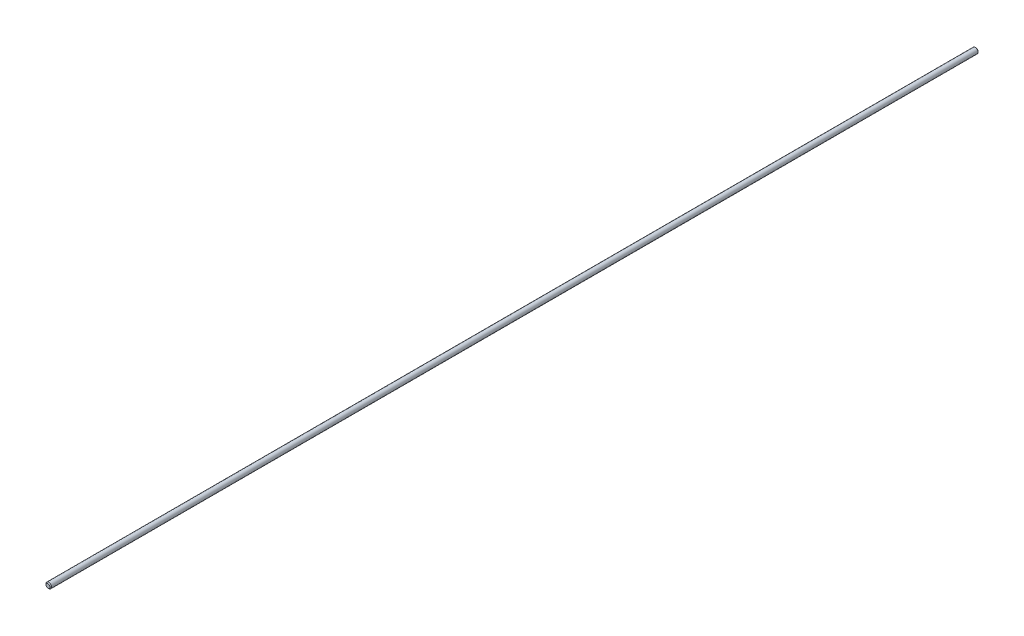
SolidWorks part; units mm, degrees
material "AISI 316 Stainless Steel Sheet (SS)"
ref_plane "Front Plane" through (0, 0, 0) normal (0, 0, 1) x (1, 0, 0)
ref_plane "Top Plane" through (0, 0, 0) normal (0, 1, 0) x (1, 0, 0)
ref_plane "Right Plane" through (0, 0, 0) normal (1, 0, 0) x (0, 0, -1)
sketch "Sketch1" plane through (0, 0, 0) normal (1, 0, 0) x (0, 0, -1)
  line L0 (-266.065, 0) -> (266.065, 0) construction
  line L1 (-266.065, 0) -> (-266.065, 1.5875)
  line L2 (-266.065, 1.5875) -> (266.065, 1.5875)
  line L3 (266.065, 1.5875) -> (266.065, 0)
  line L4 (266.6603, 1.1063) -> (266.3428, 1.6562) construction
  line L5 (266.3428, 1.6562) -> (266.0253, 1.1063) construction
  line L6 (266.0253, 1.1063) -> (266.6603, 1.1063) construction
  line L7 (266.6206, 1.1751) -> (266.065, 1.1751) construction
  line L8 (266.3428, 1.1063) -> (266.3428, 1.1751) construction
  line L9 (266.3428, 1.1751) -> (266.3428, 1.5875) construction
  line L10 (266.3428, 1.5875) -> (266.3428, 1.6562) construction
  line L15 (266.3825, 1.5875) -> (266.3031, 1.5875)
  line L16 (266.6405, 1.1407) -> (266.0452, 1.1407)
  line L17 (266.3031, 1.5875) -> (266.0452, 1.1407)
  line L18 (266.3825, 1.5875) -> (266.6405, 1.1407)
  line L19 (266.065, 0) -> (266.065, -1.5875) construction
  point P17 (266.3428, 1.1407)
  point P18 (253.365, 0)
  point P19 (264.795, -1.5875)
  point P20 (240.665, 0)
  point P22 (-253.365, 0)
  dimension "Length" = 532.13
  dimension "Thread size" = 3.175
  dimension "Pitch" = 0.635
  dimension "D2" = 0.0794
  dimension "D1" = 1.27
  dimension "Segment" = 25.4
  dimension "D3" = 12.7
  dimension "D4" = 12.7
sketch "Sketch2" plane through (0, 0, 0) normal (1, 0, 0) x (0, 0, -1)
  line L0 (266.065, 1.5875) -> (266.065, 0) construction
  line L1 (-266.065, 1.5875) -> (266.065, 1.5875) construction
  line L2 (-266.065, 0) -> (-266.065, 1.5875) construction
  line L3 (266.065, 1.5875) -> (266.065, 0)
  line L4 (-266.065, 1.5875) -> (266.065, 1.5875)
  line L5 (-266.065, 0) -> (-266.065, 1.5875)
  line L6 (-266.065, 0) -> (266.065, 0)
revolve "Revolve1" add sketch "Sketch2" angle 360 about L6
chamfer "Chamfer1" distance 0.4763 angle 45 2 edges at (1.5875, 0, -266.065) (1.5875, 0, 266.065)
sketch "Sketch3" [suppressed] plane through (0, 0, -304.8) normal (0, 0, -1) x (-1, 0, 0)
  circle A0 centre (0, 0) radius 1.1751
extrude "Cut-Extrude1" [suppressed] cut sketch "Sketch3" against normal through all flip side to cut
sketch "Sketch4" [suppressed] plane through (0, 0, -304.8) normal (0, 0, -1) x (-1, 0, 0)
  circle A1 centre (0, 0) radius 1.1751
  circle A2 centre (0, 0) radius 1.1751
  dimension "D1" = 0
ref_plane "Plane1" [suppressed] through (0, 0, 304.8) normal (0, 0, 1) x (1, 0, 0)
curve "Helix/Spiral1" [suppressed] pitch 0.635 height 26.035 turns 41
sketch "Sketch5" [suppressed] plane through (0, 0, 0) normal (1, 0, 0) x (0, 0, -1)
  line L0 (305.1175, 1.5875) -> (305.0381, 1.5875) construction
  line L1 (305.0381, 1.5875) -> (304.7802, 1.1407) construction
  line L2 (305.3755, 1.1407) -> (304.7802, 1.1407) construction
  line L3 (305.1175, 1.5875) -> (305.3755, 1.1407) construction
  line L4 (305.1175, 1.5875) -> (305.0381, 1.5875)
  line L5 (305.0381, 1.5875) -> (304.7802, 1.1407)
  line L6 (305.3755, 1.1407) -> (304.7802, 1.1407)
  line L7 (305.1175, 1.5875) -> (305.3755, 1.1407)
sweep "Sweep1" [suppressed] add profiles "Sketch5" path "Helix/Spiral1"
pattern_linear "LPattern1" [suppressed] count 22 spacing 25.4 along (0, 0, 1) of bodies 136
other "SurfaceCut1" [suppressed]
sketch "Sketch6" [suppressed] plane through (0, 0, 0) normal (1, 0, 0) x (0, 0, -1)
  line L0 (304.8, 1.1112) -> (304.3237, 1.5875)
  line L1 (304.8, 1.5875) -> (304.8, 0) construction
  line L3 (-304.8, 1.5875) -> (304.8, 1.5875) construction
  line L4 (304.3237, 1.5875) -> (304.3238, 1.6562)
  line L5 (304.3238, 1.6562) -> (305.3953, 1.6562)
  line L6 (305.3953, 1.6562) -> (305.3953, 1.1112)
  line L7 (305.3953, 1.1112) -> (304.8, 1.1112)
  dimension "D1" = 45
  dimension "D2" = 0.4763
revolve "Cut-Revolve1" [suppressed] cut sketch "Sketch6" angle 360 about L0
mirror "Mirror1" [suppressed] about plane through (0, 0, 0) normal (0, 0, 1)
sketch "Sketch7" plane through (0, 0, -266.065) normal (0, 0, -1) x (-1, 0, 0)
  circle A0 centre (0, 0) radius 6.5324
extrude "Cut-Extrude2" [suppressed] cut sketch "Sketch7" against normal blind 35.306
ref_axis "Axis1" through (0, 0, 312.5597) along (0, 0, -1)
equation "\"D2@Sketch1\"=\"Pitch@Sketch1\"/8"
equation "\"D2@Sketch1\" = \"Pitch@Sketch1\" / 8"
equation "\"D1@Sketch1\"=\"Pitch@Sketch1\"*2"
equation "\"Segment@Sketch1\" = \"Pitch@Sketch1\" * 40"
equation "\"D4@Sketch1\"=\"D3@Sketch1\""
equation "\"D1@Chamfer1\"=\"pitch@sketch1\"*0.75"
equation "\"D3@Helix/Spiral1\"=\"segment@sketch1\"+\"pitch@sketch1\""
equation "\"D4@Helix/Spiral1\"=\"pitch@sketch1\""
equation "\"D3@LPattern1\"=\"segment@sketch1\""
equation "\"D1@LPattern1\"=\"length@sketch1\"/\"segment@sketch1\"+1"
equation "\"D2@Sketch6\"=\"pitch@sketch1\"*0.75"
equation "\"Length@Sketch1\"=18.0000in+4.5-1.876+0.5-.705-0.125+0.656+0.5-0.25-0.25"
